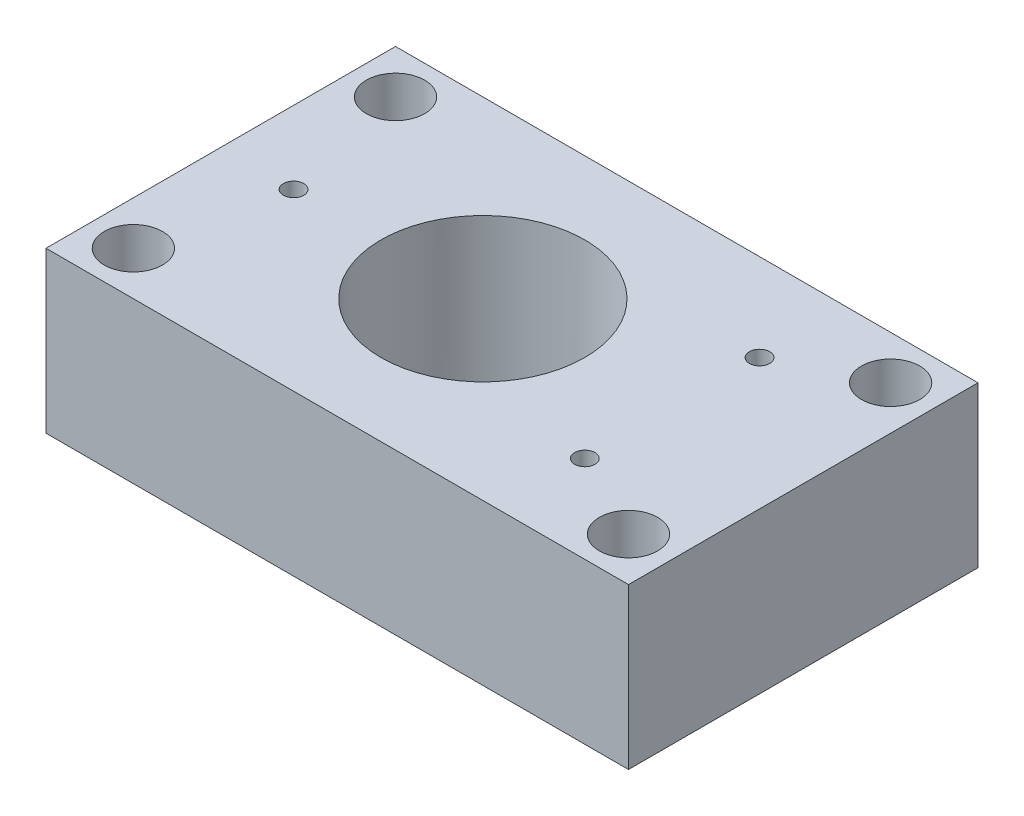
SolidWorks part; units mm, degrees
ref_plane "前视基准面" through (0, 0, 0) normal (0, 0, 1) x (1, 0, 0)
ref_plane "上视基准面" through (0, 0, 0) normal (0, 1, 0) x (1, 0, 0)
ref_plane "右视基准面" through (0, 0, 0) normal (1, 0, 0) x (0, 0, -1)
other "Configuration Table"
sketch "草图1" plane through (0, 0, 0) normal (0, 1, 0) x (1, 0, 0)
  line L1 (0, 0) -> (20, 0)
  line L2 (0, 0) -> (0, -12)
  line L3 (0, -12) -> (20, -12)
  line L4 (20, 0) -> (20, -12)
  circle A10 centre (9, -6) radius 3.5
  circle A11 centre (15, -6) radius 2.65
  point P11 (0, 0)
  dimension "D2" = 5.3
  dimension "D6" = 7
  dimension "D4" = 20
  dimension "D11" = 12
extrude "凸台-拉伸1" add sketch "草图1" along normal blind 5.5 contours L3 L4 L1 L2 | A10
extrude "切除-拉伸8" cut sketch "草图1<17>" along normal blind 1.6 contours A11
sketch "草图1<17>" plane through (0, 0, 0) normal (0, 1, 0) x (1, 0, 0) same geometry as "草图1"
sketch "草图3" plane through (0, 0, 0) normal (0, 1, 0) x (1, 0, 0)
  circle A14 centre (1.5, -1.5) radius 0.75
  circle A15 centre (18.5, -1.5) radius 0.75
  circle A16 centre (1.5, -10.5) radius 0.75
  circle A17 centre (18.5, -10.5) radius 0.75
  circle A18 centre (1.5, -1.5) radius 1
  circle A19 centre (18.5, -1.5) radius 1
  circle A20 centre (18.5, -10.5) radius 1
  circle A21 centre (1.5, -10.5) radius 1
  circle A22 centre (15.5, -3) radius 0.35
  circle A23 centre (2.5, -6) radius 0.35
  circle A24 centre (15.5, -9) radius 0.35
  point P18 (0, 0)
  point P19 (0, 0)
  point P20 (0, 0)
  dimension "D1" = 2
  dimension "D2" = 1.5
  dimension "D3" = 0.7
  dimension "D4" = 1.5
  dimension "D5" = 10.5
  dimension "D6" = 1.5
  dimension "D7" = 18.5
extrude "切除-拉伸3" cut sketch "草图3" along normal through all both and the other way through all contours A14 | A16 | A17 | A15 | A22 | A24 | A23
extrude "切除-拉伸4" cut sketch "草图3<5>" against normal offset from surface (4.5 mm away) 1 from surface contours A21 | A18 | A19 | A20 up to face at (1.5, 0, 11.25) starting at face at (1.5, 5.5, 11.25)
sketch "草图3<5>" plane through (0, 0, 0) normal (0, 1, 0) x (1, 0, 0) same geometry as "草图3"
